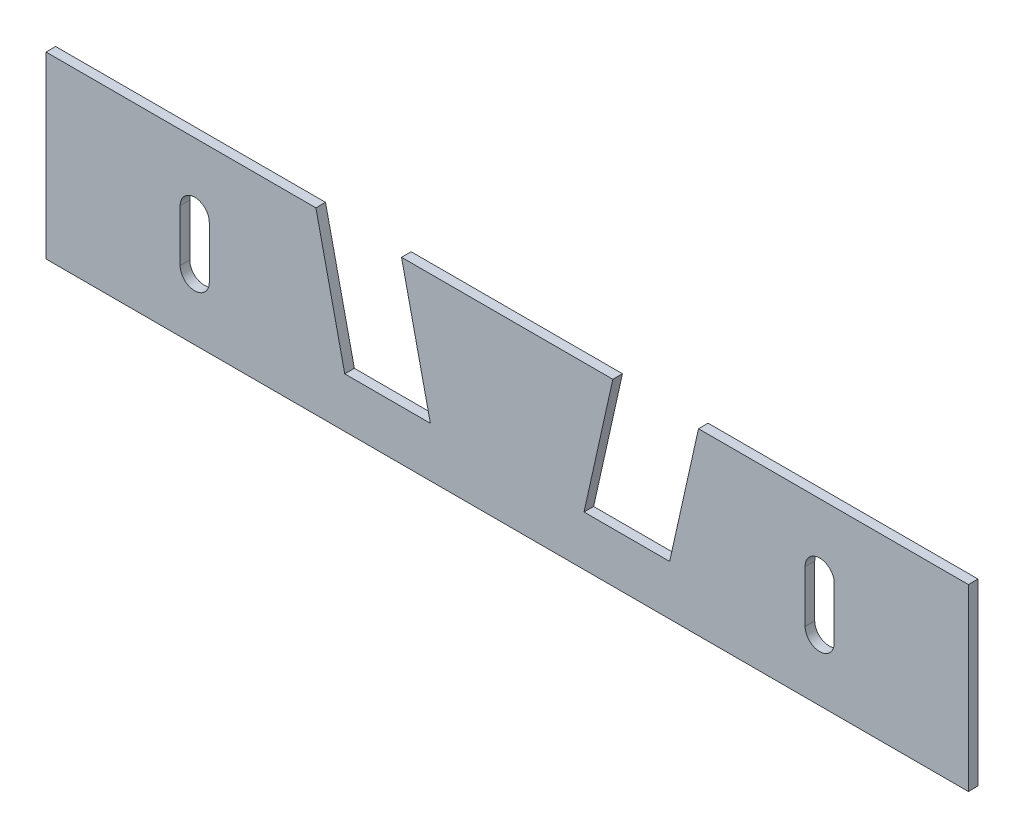
SolidWorks part; units mm, degrees
ref_plane "Спереди" through (0, 0, 0) normal (0, 0, 1) x (1, 0, 0)
ref_plane "Сверху" through (0, 0, 0) normal (0, 1, 0) x (1, 0, 0)
ref_plane "Справа" through (0, 0, 0) normal (1, 0, 0) x (0, 0, -1)
sketch "Эскиз1" plane through (0, 0, 0) normal (0, 0, 1) x (1, 0, 0)
  line L0 (-19.9097, -34.7962) -> (-16.9078, -48.261)
  line L5 (-48, -34.7962) -> (-19.9097, -34.7962)
  line L6 (-48, -34.7962) -> (-48, -53.4542)
  line L7 (-48, -53.4542) -> (48, -53.4542)
  line L8 (48, -34.7962) -> (48, -53.4542)
  line L9 (-16.9078, -48.261) -> (-7.9953, -48.261)
  line L10 (-7.9953, -48.261) -> (-10.9972, -34.7962)
  line L11 (-10.9972, -34.7962) -> (10.9972, -34.7962)
  line L12 (10.9972, -34.7962) -> (7.9953, -48.261)
  line L13 (7.9953, -48.261) -> (16.9078, -48.261)
  line L14 (16.9078, -48.261) -> (19.9097, -34.7962)
  line L15 (19.9097, -34.7962) -> (48, -34.7962)
  line L16 (-10.9972, -34.7962) -> (10.9972, -34.7962)
  circle A0 centre (32.5214, -44.3645) radius 1.5
  circle A1 centre (-32.5214, -44.3645) radius 1.5
extrude "Бобышка-Вытянуть1" add sketch "Эскиз1" along normal blind 1 contours L15 L14 L13 L12 L11 L10 L9 L0 L5 L6 L7 L8 A1 A0 region at (0, -44.5285, 0)
sketch "Эскиз2" plane through (0, 0, 1) normal (0, 0, 1) x (1, 0, 0)
  line L0 (-32.5214, -47.0664) -> (-32.5214, -41.6627) construction
  line L1 (-34.0371, -47.0664) -> (-34.0371, -41.6627)
  line L2 (-31.0058, -47.0664) -> (-31.0058, -41.6627)
  line L3 (0, -53.4542) -> (0, -30.1683) construction
  line L4 (-48, -53.4542) -> (48, -53.4542) construction
  line L5 (32.5214, -47.0664) -> (32.5214, -41.6627) construction
  line L6 (34.0371, -47.0664) -> (34.0371, -41.6627)
  line L7 (31.0058, -47.0664) -> (31.0058, -41.6627)
  arc A0 (-34.0371, -47.0664) -> (-31.0058, -47.0664) centre (-32.5214, -47.0664) ccw
  arc A1 (-31.0058, -41.6627) -> (-34.0371, -41.6627) centre (-32.5214, -41.6627) ccw
  arc A2 (34.0371, -47.0664) -> (31.0058, -47.0664) centre (32.5214, -47.0664) cw
  arc A3 (31.0058, -41.6627) -> (34.0371, -41.6627) centre (32.5214, -41.6627) cw
  point P2 (-32.5214, -44.3645)
  point P15 (32.5214, -44.3645)
extrude "Вырез-Вытянуть1" cut sketch "Эскиз2" against normal blind 10
